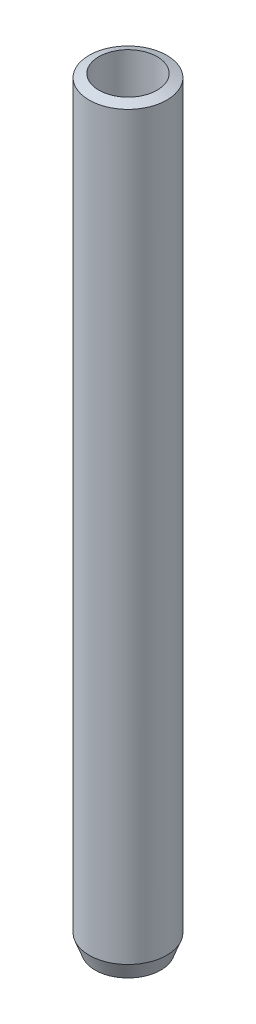
SolidWorks part; units mm, degrees
ref_plane "Front Plane" through (0, 0, 0) normal (0, 0, 1) x (1, 0, 0)
ref_plane "Top Plane" through (0, 0, 0) normal (0, 1, 0) x (1, 0, 0)
ref_plane "Right Plane" through (0, 0, 0) normal (1, 0, 0) x (0, 0, -1)
sketch "Sketch1" plane through (0, 0, 0) normal (0, 1, 0) x (1, 0, 0)
  circle A0 centre (0, 0) radius 12.5
  dimension "SHAFT_OD" = 25
extrude "Boss-Extrude1" add sketch "Sketch1" along normal blind 245.3583
sketch "Sketch2" plane through (0, 0, 0) normal (0, 1, 0) x (1, 0, 0)
  circle A0 centre (0, 0) radius 9.3656
  dimension "BORE_D" = 18.7312
extrude "Cut-Extrude1" cut sketch "Sketch2" along normal through all
chamfer "Chamfer1" distance 1.933 angle 69.339 2 edges at (0, 245.3583, 12.5) (0, 0, 12.5) first distance on face at (0, 245.3583, 12.5) first distance on face at (0, 0, 9.3656)
